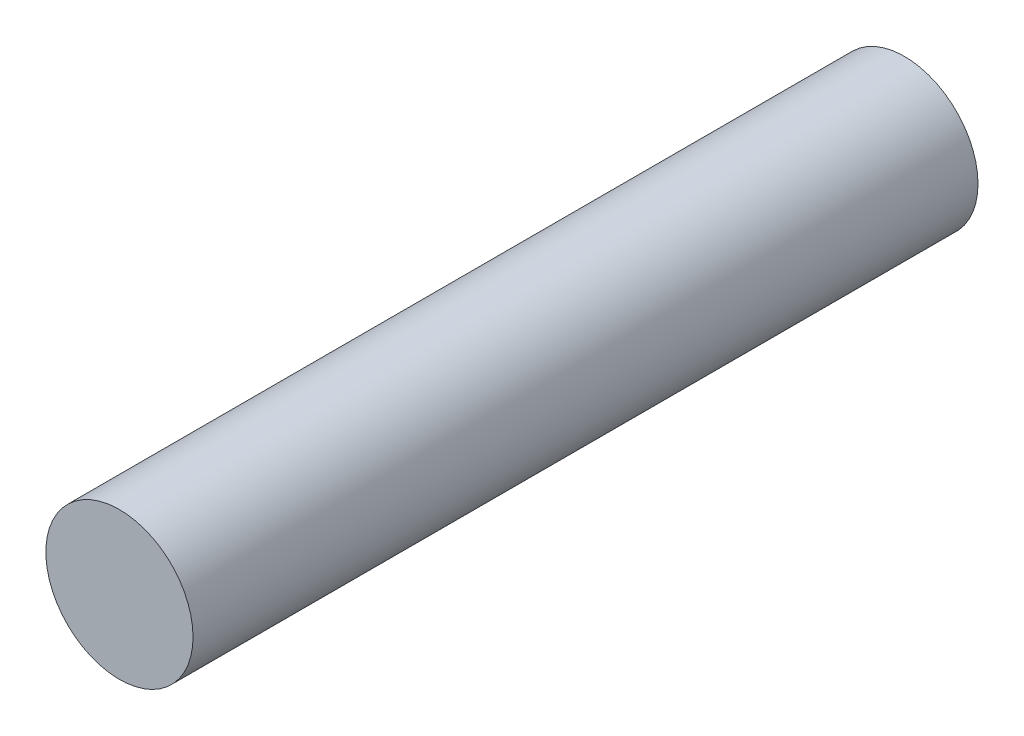
SolidWorks part; units mm, degrees
ref_plane "정면" through (0, 0, 0) normal (0, 0, 1) x (1, 0, 0)
ref_plane "윗면" through (0, 0, 0) normal (0, 1, 0) x (1, 0, 0)
ref_plane "우측면" through (0, 0, 0) normal (1, 0, 0) x (0, 0, -1)
sketch "스케치2" plane through (0, 0, 0) normal (0, 0, 1) x (1, 0, 0)
  circle A0 centre (0, 0) radius 4
  circle A1 centre (0, 0) radius 7.5
  dimension "D1" = 8
  dimension "D2" = 15
extrude "보스-돌출1" add sketch "스케치2" along normal blind 80 contours A1
extrude "컷-돌출1" cut sketch "스케치2<3>" along normal blind 30 contours A0 region at (0, 0, 0)
sketch "스케치2<3>" plane through (0, 0, 0) normal (0, 0, 1) x (1, 0, 0) same geometry as "스케치2"
